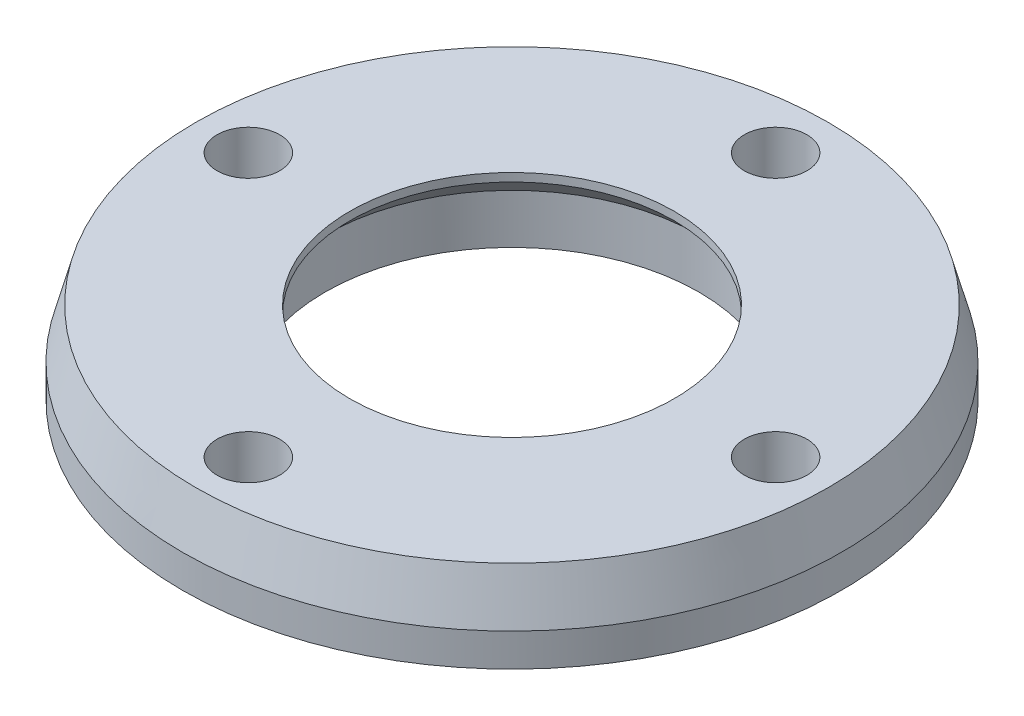
SolidWorks part; units mm, degrees
material "ABS"
ref_plane "Front Plane" through (0, 0, 0) normal (0, 0, 1) x (1, 0, 0)
ref_plane "Top Plane" through (0, 0, 0) normal (0, 1, 0) x (1, 0, 0)
ref_plane "Right Plane" through (0, 0, 0) normal (1, 0, 0) x (0, 0, -1)
sketch "Sketch1" plane through (0, 0, 0) normal (0, 1, 0) x (1, 0, 0)
  circle A0 centre (0, 0) radius 20
  circle A1 centre (0, 0) radius 11.35
  circle A2 centre (0, 16) radius 1.9
  circle A3 centre (16, 0) radius 1.9
  circle A4 centre (0, -16) radius 1.9
  circle A5 centre (-16, 0) radius 1.9
  point P19 (0, 0)
  dimension "D1" = 22.7
  dimension "D2" = 40
  dimension "D5" = 3.8
  dimension "D3" = 16
  dimension "D4" = 4
extrude "Boss-Extrude1" add sketch "Sketch1" along normal blind 5
chamfer "Chamfer1" distance 3 angle 15 1 edges at (0, 5, 20) first distance on face at (0, 5, 20)
sketch "Sketch2" plane through (0, 5, 0) normal (0, 1, 0) x (1, 0, 0)
  circle A0 centre (0, 0) radius 11.35
  circle A1 centre (0, 0) radius 9.85
  dimension "D1" = 19.7
  dimension "D2" = 22.7
extrude "Boss-Extrude2" add sketch "Sketch2" against normal blind 2
chamfer "Chamfer2" distance 1.5 angle 45 1 edges at (0, 3, 9.85)
